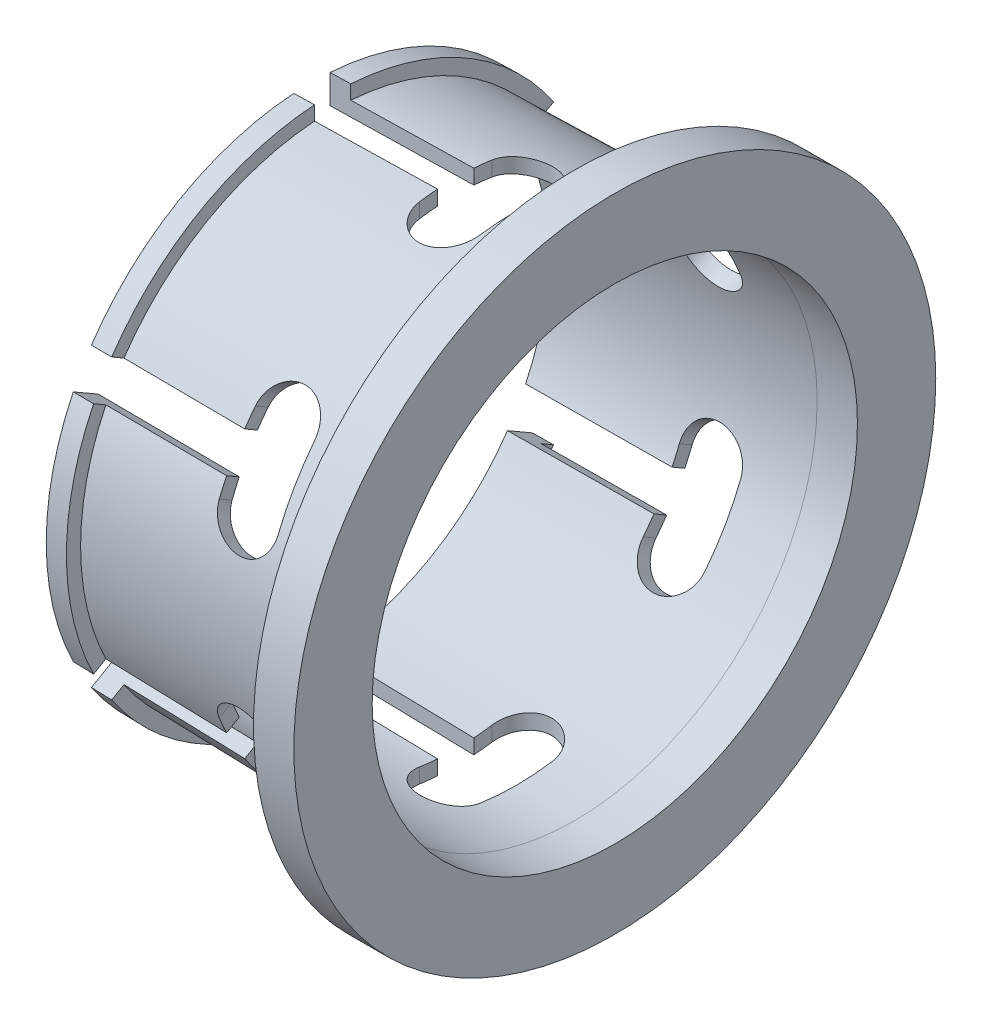
SolidWorks part; units mm, degrees
other "Markup1"
sketch "Sketch5" plane through (-96.0567, 101.1339, 101.1339) normal (-0.5898, 0.2179, 0.7776) x (0.7941, -0.0186, 0.6075)
ref_plane "Front Plane" through (0, 0, 0) normal (0, 0, 1) x (1, 0, 0)
ref_plane "Top Plane" through (0, 0, 0) normal (0, 1, 0) x (1, 0, 0)
ref_plane "Right Plane" through (0, 0, 0) normal (1, 0, 0) x (0, 0, -1)
sketch "Sketch3" plane through (0, 0, 0) normal (0, 0, 1) x (1, 0, 0)
  line L0 (0, 0) -> (0, 76.454) construction
  line L1 (0, 76.454) -> (-12.7, 76.454)
  line L2 (0, 76.454) -> (0, 101.1339)
  line L3 (0, 101.1339) -> (-12.7, 101.1339)
  line L4 (-12.7, 101.1339) -> (-12.7, 81.0665)
  line L5 (-12.7, 81.0665) -> (-88.916, 79.4097)
  line L6 (-88.916, 79.4097) -> (-88.916, 83.8672)
  line L7 (-88.916, 83.8672) -> (-95.4261, 83.7257)
  line L8 (-95.4261, 83.7257) -> (-95.4261, 74.6556)
  line L9 (-95.4261, 74.6556) -> (-12.7, 76.454)
  line L10 (0, 0) -> (-96.0567, 0) construction
  point P12 (-95.6927, 76.454)
  point P13 (-95.1595, 74.6614)
  point P14 (-95.4261, 83.7257)
  dimension "D1" = 76.454
  dimension "D2" = 12.7
revolve "Revolve1" add sketch "Sketch3" angle 360 about L10
sketch "Sketch4" plane through (0, 0, 0) normal (0, 1, 0) x (1, 0, 0)
  line L0 (-95.4261, 5.715) -> (-95.4261, -5.715)
  line L1 (-95.4261, 83.7257) -> (-95.4261, -83.7257) construction
  line L2 (-95.4261, 83.7257) -> (-95.4261, -83.7257) construction
  line L3 (-95.4261, -5.715) -> (-50.1307, -5.715)
  line L4 (-95.4261, 5.715) -> (-50.1307, 5.715)
  line L6 (-40.6268, 11.3843) -> (-40.6268, -11.3843) construction
  line L7 (-31.1229, 11.3843) -> (-31.1229, -11.3843)
  line L8 (-50.1307, 11.3843) -> (-50.1307, 5.715)
  line L9 (-50.1307, -5.715) -> (-50.1307, -11.3843)
  arc A0 (-31.1229, 11.3843) -> (-50.1307, 11.3843) centre (-40.6268, 11.3843) ccw
  arc A1 (-50.1307, -11.3843) -> (-31.1229, -11.3843) centre (-40.6268, -11.3843) ccw
  point P0 (-53.1791, 111.8078)
  point P6 (-95.4261, 0)
  point P10 (-40.6268, 0)
  dimension "D1" = 11.43
extrude "Cut-Extrude1" cut sketch "Sketch4" against normal up to surface (84.3589 mm away) contours A0 L8 L4 L0 L3 L9 A1 L7 up to face at (-95.4261, 0, -83.7257)
pattern_circular "CirPattern1" count 6 over 360 about axis through (-95.4261, 0, 0) along (-1, 0, 0) of "Cut-Extrude1"
